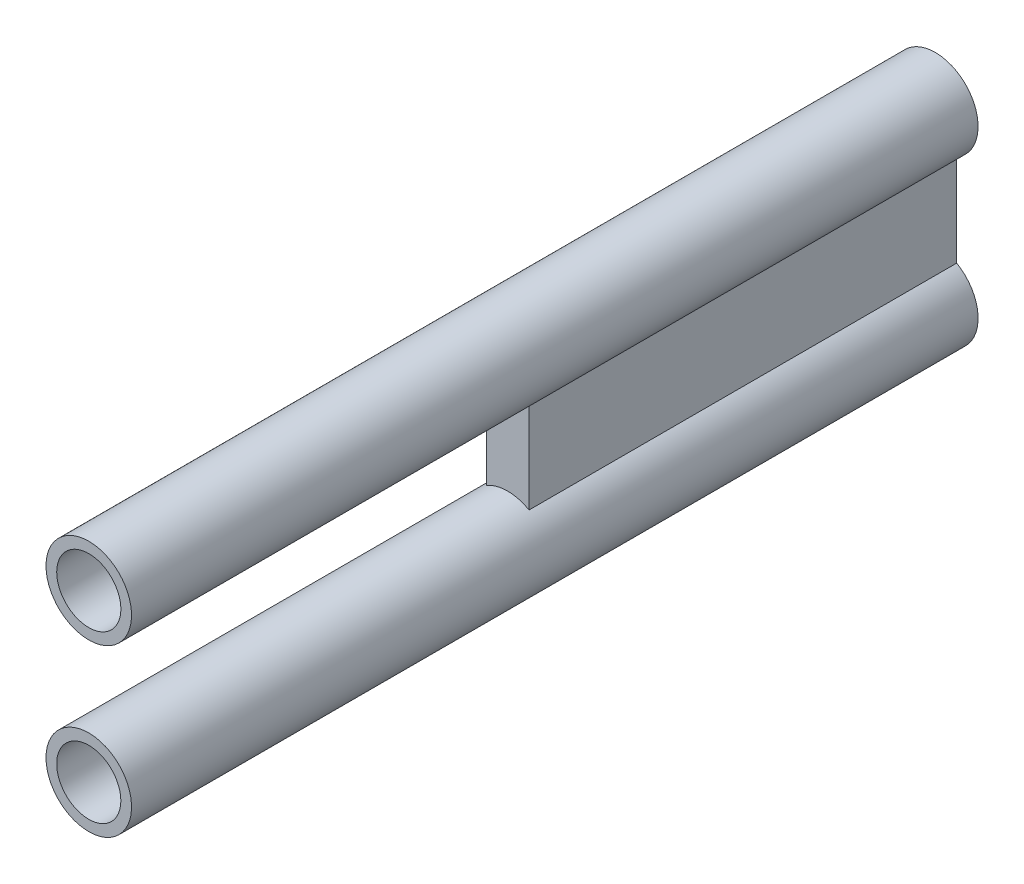
SolidWorks part; units mm, degrees
ref_plane "Plan de face" through (0, 0, 0) normal (0, 0, 1) x (1, 0, 0)
ref_plane "Plan de dessus" through (0, 0, 0) normal (0, 1, 0) x (1, 0, 0)
ref_plane "Plan de droite" through (0, 0, 0) normal (1, 0, 0) x (0, 0, -1)
sketch "Esquisse1" plane through (0, 0, 0) normal (0, 0, 1) x (1, 0, 0)
  line L0 (0, 3.8821) -> (0, -3.8821) construction
  line L2 (1, -2.15) -> (1, 2.15)
  line L4 (-1, -2.15) -> (-1, 2.15)
  line L5 (1, -2.15) -> (-1, 2.15) construction
  line L6 (1, 2.15) -> (-1, -2.15) construction
  circle A0 centre (0, 3.8821) radius 2
  circle A1 centre (0, -3.8821) radius 2
  circle A2 centre (0, -3.8821) radius 1.5
  circle A3 centre (0, 3.8821) radius 1.5
  point P4 (0, 0)
  point P12 (0, 0)
  dimension "D1" = 4
  dimension "D2" = 0.5
  dimension "D5" = 4
  dimension "D6" = 0.5
  dimension "D3" = 2
  dimension "D4" = 4.3
extrude "Boss.-Extru.1" add sketch "Esquisse1" along normal up to surface (39.5885 mm away) contours A0 | A1 region at (1.6831, -2.9103, 0) region at (0, 1.9386, 0)
extrude "Boss.-Extru.2" add sketch "Esquisse1<3>" along normal blind 20 contours A1 L2 A0 L4 region at (0, 0, 0)
sketch "Esquisse1<3>" plane through (0, 0, 0) normal (0, 0, 1) x (1, 0, 0) same geometry as "Esquisse1"
